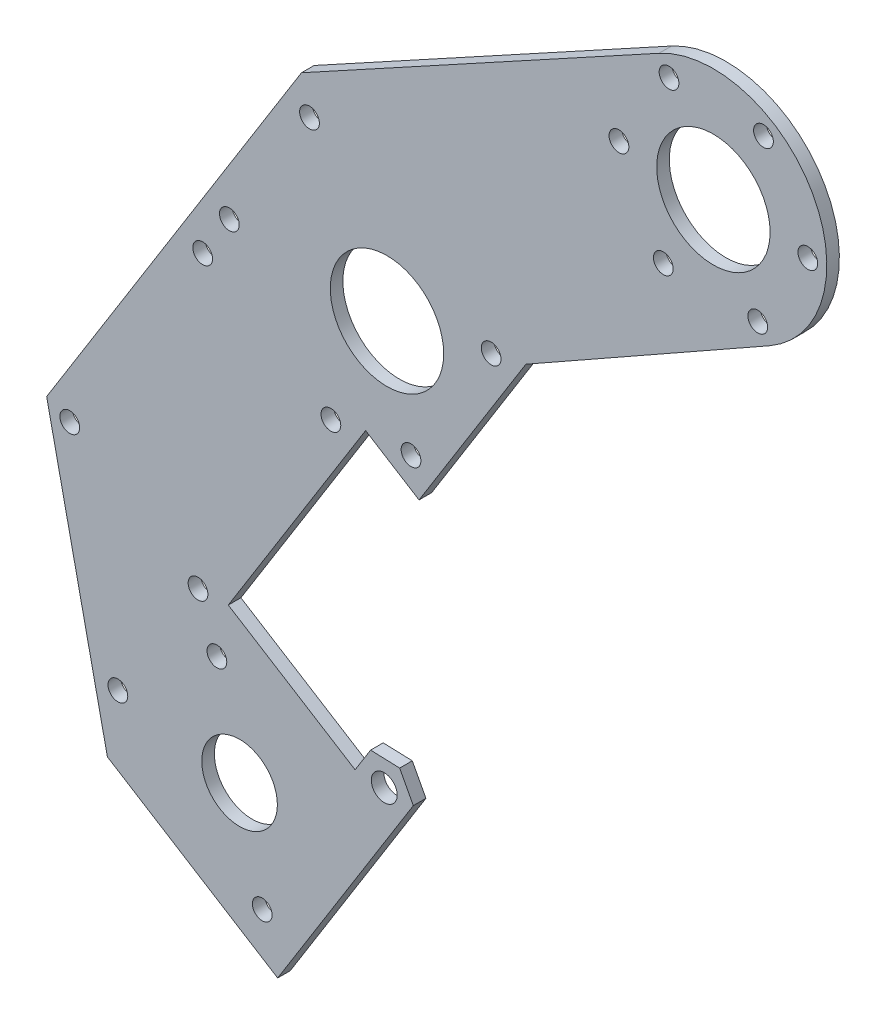
SolidWorks part; units mm, degrees
material "6061 Alloy"
ref_plane "Front Plane" through (0, 0, 0) normal (0, 0, 1) x (1, 0, 0)
ref_plane "Top Plane" through (0, 0, 0) normal (0, 1, 0) x (1, 0, 0)
ref_plane "Right Plane" through (0, 0, 0) normal (1, 0, 0) x (0, 0, -1)
sketch "Sketch1" plane through (0, 0, -14.1946) normal (0, 0, 1) x (1, 0, 0)
  line L0 (-11.4036, 461.0409) -> (18.8813, 509.5069)
  line L1 (-54.3079, 487.8505) -> (-69.6155, 558.824)
  line L2 (8.1111, 516.2368) -> (-23.8465, 536.2061)
  line L3 (10.7592, 591.5868) -> (-157.4902, 322.3315) construction
  line L4 (-11.4036, 461.0409) -> (-54.3079, 487.8505)
  line L5 (-69.6155, 558.824) -> (-5.4017, 661.5875)
  line L6 (-23.8465, 536.2061) -> (10.7592, 591.5868)
  line L8 (-115.7964, 730.5698) -> (48.4493, 627.9377) construction
  line L9 (-142.7163, 687.4889) -> (24.222, 583.1743) construction
  line L10 (51.1419, 626.2552) -> (112.462, 660.9373)
  line L11 (10.7592, 591.5868) -> (24.222, 583.1743)
  line L13 (24.222, 583.1743) -> (51.1419, 626.2552)
  line L16 (-5.4017, 661.5875) -> (84.678, 710.8773)
  line L17 (16.1415, 618.1747) -> (-107.7159, 695.5694) construction
  line L18 (18.8813, 509.5069) -> (22.7847, 515.7536)
  line L19 (-23.8465, 536.2061) -> (-52.9124, 489.691) construction
  line L20 (-4.9986, 524.4287) -> (-34.0645, 477.9135) construction
  line L22 (12.0145, 522.4836) -> (8.1111, 516.2368)
  line L23 (12.0145, 522.4836) -> (19.3423, 522.2277)
  line L24 (19.3423, 522.2277) -> (22.7847, 515.7536)
  line L25 (17.3996, 519.1186) -> (21.0569, 524.9715) construction
  circle A2 centre (16.1415, 618.1747) radius 14.2875
  circle A5 centre (98.3945, 685.8096) radius 14.2875
  arc A7 (112.462, 660.9373) -> (84.678, 710.8773) centre (98.3945, 685.8096) ccw
  circle A8 centre (-107.7159, 695.5694) radius 215.011 construction
  circle A9 centre (-21.0004, 498.8205) radius 9.525
  point P33 (98.3945, 685.8096)
  dimension "D1" = 22.225
  dimension "D2" = 19.05
  dimension "D3" = 7.366
  dimension "D4" = 120
extrude "Boss-Extrude1" add sketch "Sketch1" along normal blind 3.175
sketch "Sketch17" plane through (0, 0, -11.0196) normal (0, 0, 1) x (1, 0, 0)
  line L0 (-4.9986, 524.4287) -> (-34.0645, 477.9135) construction
  line L2 (16.1415, 618.1747) -> (37.6819, 604.7147) construction
  line L11 (-26.7141, 523.5695) -> (-15.2866, 474.0715) construction
  line L12 (24.222, 583.1743) -> (51.1419, 626.2552) construction
  line L13 (37.6819, 604.7147) -> (27.587, 588.5594) construction
  line L14 (27.587, 588.5594) -> (22.2019, 591.9244) construction
  line L15 (22.2019, 591.9244) -> (-28.9566, 623.8918) construction
  line L16 (-5.4017, 661.5875) -> (-69.6155, 558.824) construction
  line L17 (-28.9566, 623.8918) -> (-23.5715, 620.5268) construction
  line L18 (-23.5715, 620.5268) -> (-3.3816, 652.8374) construction
  line L19 (-3.3816, 652.8374) -> (42.3918, 624.2351) construction
  line L20 (10.7592, 591.5868) -> (5.3741, 594.9518) construction
  line L21 (5.3741, 594.9518) -> (-31.4748, 535.9811) construction
  line L22 (-31.4748, 535.9811) -> (-51.6648, 503.6705) construction
  line L23 (5.3741, 594.9518) -> (2.0091, 589.5667) construction
  line L24 (-31.4748, 535.9811) -> (-63.7855, 556.1711) construction
  line L25 (2.0091, 589.5667) -> (-30.3015, 609.7566) construction
  circle A1 centre (-21.0004, 498.8205) radius 25.4 construction
  circle A2 centre (15.4568, 516.0095) radius 6.35 construction
  point P32 (-21.0004, 498.8205)
  dimension "D1" = 45
hole_wizard "#10 Clearance Hole2" positions "Sketch20" profile "Sketch21" hole size "#10" standard "ANSI Inch" end condition through all
sketch "Sketch20" plane through (0, 0, -11.0196) normal (0, 0, 1) x (1, 0, 0)
  point P0 (-26.7141, 523.5695)
  point P3 (-15.2866, 474.0715)
  point P24 (-3.3816, 652.8374)
  point P27 (42.3918, 624.2351)
  point P30 (22.2019, 591.9244)
  point P33 (-23.5715, 620.5268)
  point P42 (-31.4748, 535.9811)
  point P45 (-63.7855, 556.1711)
  point P48 (-51.6648, 503.6705)
  point P54 (2.0091, 589.5667)
  point P57 (-30.3015, 609.7566)
  point P60 (-16.6195, 473.8011)
  point P62 (-25.3812, 523.8398)
sketch "Sketch21" plane through (-26.7141, 523.5695, -11.0196) normal (1, 0, 0) x (0, -1, 0)
  line L0 (0, 0) -> (0, 3.175)
  line L1 (0, 3.175) -> (2.4892, 3.175)
  line L2 (2.4892, 3.175) -> (2.4892, 0)
  line L5 (2.4892, 0) -> (0, 0)
  line L11 (0, -6.35) -> (0, 107.95) construction
  dimension "Thru Hole Dia." = 4.9784
  dimension "Thru Hole Depth" = 3.175
sketch "Sketch22" plane through (0, 0, -11.0196) normal (0, 0, 1) x (1, 0, 0)
  line L0 (98.3945, 685.8096) -> (111.0132, 706.0038) construction
  line L2 (111.0132, 706.0038) -> (87.2152, 706.8348) construction
  line L3 (87.2152, 706.8348) -> (74.5965, 686.6407) construction
  line L4 (74.5965, 686.6407) -> (85.7758, 665.6155) construction
  line L5 (85.7758, 665.6155) -> (109.5738, 664.7845) construction
  line L6 (109.5738, 664.7845) -> (122.1925, 684.9786) construction
  line L7 (122.1925, 684.9786) -> (111.0132, 706.0038) construction
  circle A0 centre (98.3945, 685.8096) radius 23.8125 construction
hole_wizard "#10 Clearance Hole3" positions "Sketch23" profile "Sketch24" hole size "#10" standard "ANSI Inch" end condition through all
sketch "Sketch23" plane through (0, 0, -11.0196) normal (0, 0, 1) x (1, 0, 0)
  point P0 (111.0132, 706.0038)
  point P3 (122.1925, 684.9786)
  point P6 (109.5738, 664.7845)
  point P9 (85.7758, 665.6155)
  point P12 (74.5965, 686.6407)
  point P15 (87.2152, 706.8348)
sketch "Sketch24" plane through (111.0132, 706.0038, -11.0196) normal (1, 0, 0) x (0, -1, 0)
  line L0 (0, 0) -> (0, 3.175)
  line L1 (0, 3.175) -> (2.4892, 3.175)
  line L2 (2.4892, 3.175) -> (2.4892, 0)
  line L5 (2.4892, 0) -> (0, 0)
  line L11 (0, -6.35) -> (0, 107.95) construction
  dimension "Thru Hole Dia." = 4.9784
  dimension "Thru Hole Depth" = 3.175
hole_wizard "1/4 Clearance Hole1" positions "Sketch25" profile "Sketch26" hole size "1/4" standard "ANSI Inch" end condition through all
sketch "Sketch25" plane through (0, 0, -11.0196) normal (0, 0, 1) x (1, 0, 0)
  point P0 (15.4568, 516.0095)
sketch "Sketch26" plane through (15.4568, 516.0095, -11.0196) normal (1, 0, 0) x (0, -1, 0)
  line L0 (0, 0) -> (0, 3.175)
  line L1 (0, 3.175) -> (3.2639, 3.175)
  line L2 (3.2639, 3.175) -> (3.2639, 0)
  line L5 (3.2639, 0) -> (0, 0)
  line L11 (0, -6.35) -> (0, 107.95) construction
  dimension "Thru Hole Dia." = 6.5278
  dimension "Thru Hole Depth" = 3.175
